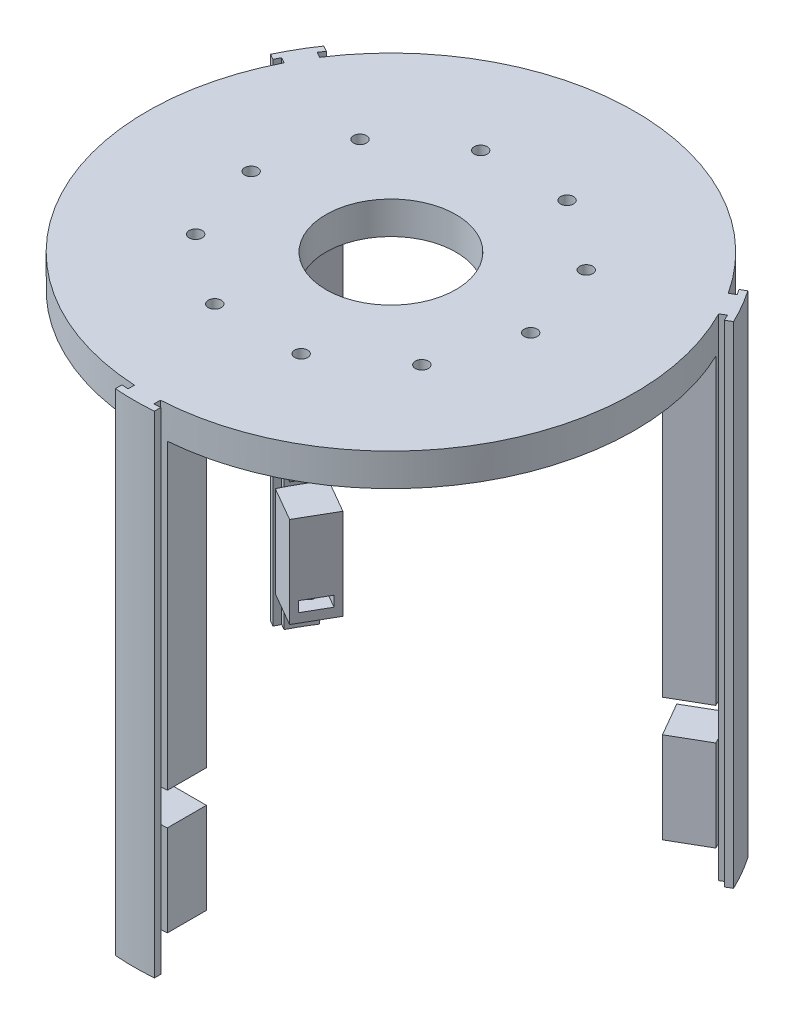
SolidWorks part; units mm, degrees
ref_plane "Front Plane" through (0, 0, 0) normal (0, 0, 1) x (1, 0, 0)
ref_plane "Top Plane" through (0, 0, 0) normal (0, 1, 0) x (1, 0, 0)
ref_plane "Right Plane" through (0, 0, 0) normal (1, 0, 0) x (0, 0, -1)
sketch "Sketch1" plane through (0, 0, 0) normal (0, 1, 0) x (1, 0, 0)
  circle A0 centre (0, 0) radius 37.5
  dimension "D1" = 75
extrude "Boss-Extrude1" add sketch "Sketch1" against normal blind 5
sketch "Sketch2" plane through (0, 0, 0) normal (0, 1, 0) x (1, 0, 0)
  line L0 (-2.75, 0) -> (2.75, 0) construction
  line L1 (0, 39.8902) -> (0, -39.5701) construction
  line L2 (0, -2.75) -> (0, 2.75) construction
  line L4 (-39.7283, 0) -> (39.0263, 0) construction
  circle A0 centre (-21.5, 0) radius 1
  circle A1 centre (-17.3939, 12.6374) radius 1
  circle A2 centre (-6.6439, 20.4477) radius 1
  circle A3 centre (6.6439, 20.4477) radius 1
  circle A4 centre (17.3939, 12.6374) radius 1
  circle A5 centre (21.5, 0) radius 1
  circle A6 centre (17.3939, -12.6374) radius 1
  circle A7 centre (6.6439, -20.4477) radius 1
  circle A8 centre (-6.6439, -20.4477) radius 1
  circle A9 centre (-17.3939, -12.6374) radius 1
  dimension "D1" = 10
  dimension "D2" = 43
extrude "Cut-Extrude1" cut sketch "Sketch2" against normal up to next
sketch "Sketch3" plane through (0, -5, 0) normal (0, -1, 0) x (1, 0, 0)
  line L0 (-3, 37.3798) -> (-3, 31.3798)
  line L1 (-3, 31.3798) -> (3, 31.3798)
  line L2 (3, 31.3798) -> (3, 37.3798)
  line L3 (33.8719, -16.0918) -> (28.6757, -13.0918)
  line L4 (28.6757, -13.0918) -> (25.6757, -18.288)
  line L5 (25.6757, -18.288) -> (30.8719, -21.288)
  line L6 (-30.8719, -21.288) -> (-25.6757, -18.288)
  line L7 (-25.6757, -18.288) -> (-28.6757, -13.0918)
  line L8 (-28.6757, -13.0918) -> (-33.8719, -16.0918)
  line L9 (0, 40.3758) -> (0, -39.6162) construction
  line L10 (0, -2.75) -> (0, 2.75) construction
  arc A0 (3, 37.3798) -> (-3, 37.3798) centre (0, 0) ccw
  arc A1 (30.8719, -21.288) -> (33.8719, -16.0918) centre (0, 0) ccw
  arc A2 (-33.8719, -16.0918) -> (-30.8719, -21.288) centre (0, 0) ccw
  circle A3 centre (0, 0) radius 37.5 construction
  point P18 (0, 0)
  dimension "D1" = 3
  dimension "D2" = 6
  dimension "D3" = 6
extrude "Boss-Extrude2" add sketch "Sketch3" along normal blind 65.5
sketch "Sketch4" plane through (0, -5, 0) normal (0, -1, 0) x (1, 0, 0)
  line L0 (-15.5255, 11.28) -> (-15.2841, 13.5767)
  line L1 (-19.1906, 0) -> (-20.3453, 2)
  line L2 (-20.3453, 2) -> (-22.6547, 2)
  line L3 (-22.6547, 2) -> (-23.8094, 0)
  line L4 (-23.8094, 0) -> (-22.6547, -2)
  line L5 (-22.6547, -2) -> (-20.3453, -2)
  line L6 (-20.3453, -2) -> (-19.1906, 0)
  line L7 (-15.2841, 13.5767) -> (-17.1525, 14.9341)
  line L8 (-17.1525, 14.9341) -> (-19.2622, 13.9948)
  line L9 (-19.2622, 13.9948) -> (-19.5036, 11.6981)
  line L10 (-19.5036, 11.6981) -> (-17.6353, 10.3406)
  line L11 (-17.6353, 10.3406) -> (-15.5255, 11.28)
  line L12 (-5.9302, 18.2513) -> (-4.3849, 19.9676)
  line L13 (-4.3849, 19.9676) -> (-5.0986, 22.1639)
  line L14 (-5.0986, 22.1639) -> (-7.3575, 22.6441)
  line L15 (-7.3575, 22.6441) -> (-8.9028, 20.9279)
  line L16 (-8.9028, 20.9279) -> (-8.1892, 18.7315)
  line L17 (-8.1892, 18.7315) -> (-5.9302, 18.2513)
  line L18 (5.9302, 18.2513) -> (8.1892, 18.7315)
  line L19 (8.1892, 18.7315) -> (8.9028, 20.9279)
  line L20 (8.9028, 20.9279) -> (7.3575, 22.6441)
  line L21 (7.3575, 22.6441) -> (5.0986, 22.1639)
  line L22 (5.0986, 22.1639) -> (4.3849, 19.9676)
  line L23 (4.3849, 19.9676) -> (5.9302, 18.2513)
  line L24 (15.5255, 11.28) -> (17.6353, 10.3406)
  line L25 (17.6353, 10.3406) -> (19.5036, 11.6981)
  line L26 (19.5036, 11.6981) -> (19.2622, 13.9948)
  line L27 (19.2622, 13.9948) -> (17.1525, 14.9341)
  line L28 (17.1525, 14.9341) -> (15.2841, 13.5767)
  line L29 (15.2841, 13.5767) -> (15.5255, 11.28)
  line L30 (19.1906, 0) -> (20.3453, -2)
  line L31 (20.3453, -2) -> (22.6547, -2)
  line L32 (22.6547, -2) -> (23.8094, 0)
  line L33 (23.8094, 0) -> (22.6547, 2)
  line L34 (22.6547, 2) -> (20.3453, 2)
  line L35 (20.3453, 2) -> (19.1906, 0)
  line L36 (15.5255, -11.28) -> (15.2841, -13.5767)
  line L37 (15.2841, -13.5767) -> (17.1525, -14.9341)
  line L38 (17.1525, -14.9341) -> (19.2622, -13.9948)
  line L39 (19.2622, -13.9948) -> (19.5036, -11.6981)
  line L40 (19.5036, -11.6981) -> (17.6353, -10.3406)
  line L41 (17.6353, -10.3406) -> (15.5255, -11.28)
  line L42 (5.9302, -18.2513) -> (4.3849, -19.9676)
  line L43 (4.3849, -19.9676) -> (5.0986, -22.1639)
  line L44 (5.0986, -22.1639) -> (7.3575, -22.6441)
  line L45 (7.3575, -22.6441) -> (8.9028, -20.9279)
  line L46 (8.9028, -20.9279) -> (8.1892, -18.7315)
  line L47 (8.1892, -18.7315) -> (5.9302, -18.2513)
  line L48 (-5.9302, -18.2513) -> (-8.1892, -18.7315)
  line L49 (-8.1892, -18.7315) -> (-8.9028, -20.9279)
  line L50 (-8.9028, -20.9279) -> (-7.3575, -22.6441)
  line L51 (-7.3575, -22.6441) -> (-5.0986, -22.1639)
  line L52 (-5.0986, -22.1639) -> (-4.3849, -19.9676)
  line L53 (-4.3849, -19.9676) -> (-5.9302, -18.2513)
  line L54 (-15.5255, -11.28) -> (-17.6353, -10.3406)
  line L55 (-17.6353, -10.3406) -> (-19.5036, -11.6981)
  line L56 (-19.5036, -11.6981) -> (-19.2622, -13.9948)
  line L57 (-19.2622, -13.9948) -> (-17.1525, -14.9341)
  line L58 (-17.1525, -14.9341) -> (-15.2841, -13.5767)
  line L59 (-15.2841, -13.5767) -> (-15.5255, -11.28)
  circle A0 centre (-21.5, 0) radius 2 construction
  dimension "D1" = 10
extrude "Cut-Extrude2" cut sketch "Sketch4" against normal blind 1.6
sketch "Sketch5" plane through (0, 0, 0) normal (0, 1, 0) x (1, 0, 0)
  line L0 (-3, -38.3602) -> (-3, -39.3859)
  line L1 (3, -38.381) -> (3, -39.3859)
  line L2 (2, -38.4461) -> (2, -37.4466)
  line L3 (-2, -38.4253) -> (-2, -37.4466)
  line L4 (-31.7209, 21.7782) -> (-32.6092, 22.291)
  line L5 (-34.739, 16.5924) -> (-35.6092, 17.0949)
  line L6 (-34.2953, 17.491) -> (-33.4297, 16.9913)
  line L7 (-32.2773, 20.9447) -> (-31.4297, 20.4554)
  line L8 (34.7209, 16.582) -> (35.6092, 17.0949)
  line L9 (31.739, 21.7886) -> (32.6092, 22.291)
  line L10 (32.2953, 20.9551) -> (31.4297, 20.4554)
  line L11 (34.2773, 17.4806) -> (33.4297, 16.9913)
  line L12 (0, 40.7328) -> (0, -41.0085) construction
  line L13 (0, -38.775) -> (0, 38.775) construction
  arc A0 (-3, -39.3859) -> (3, -39.3859) centre (0, 0) ccw
  arc A1 (-2, -37.4466) -> (2, -37.4466) centre (0, 0) ccw
  arc A2 (3, -38.381) -> (2, -38.4461) centre (0, 0) cw
  arc A3 (-3, -38.3602) -> (-2, -38.4253) centre (0, 0) ccw
  arc A4 (-32.6092, 22.291) -> (-35.6092, 17.0949) centre (0, 0) ccw
  arc A5 (-31.4297, 20.4554) -> (-33.4297, 16.9913) centre (0, 0) ccw
  arc A6 (-34.739, 16.5924) -> (-34.2953, 17.491) centre (0, 0) cw
  arc A7 (-31.7209, 21.7782) -> (-32.2773, 20.9447) centre (0, 0) ccw
  arc A8 (35.6092, 17.0949) -> (32.6092, 22.291) centre (0, 0) ccw
  arc A9 (33.4297, 16.9913) -> (31.4297, 20.4554) centre (0, 0) ccw
  arc A10 (31.739, 21.7886) -> (32.2953, 20.9551) centre (0, 0) cw
  arc A11 (34.7209, 16.582) -> (34.2773, 17.4806) centre (0, 0) ccw
  circle A12 centre (0, 0) radius 37.5 construction
  dimension "D1" = 3
  dimension "D2" = 6
  dimension "D3" = 2
  dimension "D4" = 1.0049
  dimension "D5" = 1
extrude "Boss-Extrude3" add sketch "Sketch5" against normal blind 75.5
sketch "Sketch6" plane through (0, 0, 0) normal (0, 1, 0) x (1, 0, 0)
  circle A0 centre (0, 0) radius 10
extrude "Cut-Extrude3" cut sketch "Sketch6" against normal up to next
sketch "Sketch7" plane through (0, 0, 0) normal (1, 0, 0) x (0, 0, -1)
  line L0 (0, 38.775) -> (0, -38.775) construction
  line L1 (0, -51.5) -> (-37.5, -51.5)
  line L2 (0, -51.5) -> (0, -56.5)
  line L3 (0, -56.5) -> (-37.5, -56.5)
  line L4 (-37.5, -51.5) -> (-37.5, -56.5)
  line L6 (-31.3798, -70.5) -> (-37.3798, -70.5) construction
  line L7 (0, -27.0167) -> (0, -72.0117) construction
  dimension "D1" = 37.5
  dimension "D2" = 5
  dimension "D3" = 14
revolve "Cut-Revolve1" cut sketch "Sketch7" angle 360 about L7
ref_plane "Plane5" through (0, -67.5, 0) normal (0, -1, 0) x (-1, 0, 0)
sketch "Sketch8" plane through (0, -67.5, 0) normal (0, -1, 0) x (-1, 0, 0)
  line L0 (0, 41.525) -> (0, -41.525) construction
  line L2 (-2, -31.3798) -> (-2, -35.5345)
  line L3 (-2, -35.5345) -> (0, -36.6892)
  line L4 (0, -36.6892) -> (2, -35.5345)
  line L5 (2, -35.5345) -> (2, -31.3798)
  line L7 (-3.1537, -34.3798) -> (3.1946, -34.3798) construction
  line L13 (0, -31.0997) -> (0, -37.7453) construction
  line L14 (3, -37.3798) -> (3, -31.3798) construction
  line L15 (-3, -31.3798) -> (-3, -37.3798) construction
  line L16 (-0.0081, -32.0751) -> (-2.0081, -33.2298) [skipped]
  line L17 (1.9919, -33.2204) -> (-0.0081, -32.0657) [skipped]
  line L18 (3, -31.3798) -> (-3, -31.3798) construction
  line L19 (3, -31.3798) -> (-3, -31.3798) construction
  line L20 (-2, -31.3798) -> (2, -31.3798)
  line L21 (-26.1757, 17.422) -> (-29.7738, 19.4993)
  line L22 (-29.7738, 19.4993) -> (-31.7738, 18.3446)
  line L23 (-31.7738, 18.3446) -> (-31.7738, 16.0352)
  line L24 (-31.7738, 16.0352) -> (-28.1757, 13.9579)
  line L25 (-26.1757, 17.422) -> (-28.1757, 13.9579)
  line L26 (-28.1969, 19.9211) -> (-31.3711, 14.4233) construction
  line L27 (-26.9332, 15.5499) -> (-32.6884, 18.8727) construction
  line L28 (28.1757, 13.9579) -> (31.7738, 16.0352)
  line L29 (31.7738, 16.0352) -> (31.7738, 18.3446)
  line L30 (31.7738, 18.3446) -> (29.7738, 19.4993)
  line L31 (29.7738, 19.4993) -> (26.1757, 17.422)
  line L32 (28.1757, 13.9579) -> (26.1757, 17.422)
  line L33 (31.3506, 14.4587) -> (28.1765, 19.9565) construction
  line L34 (26.9332, 15.5499) -> (32.6884, 18.8727) construction
  circle A0 centre (0, -34.3798) radius 2 construction
  circle A1 centre (-29.7738, 17.1899) radius 2 construction
  circle A2 centre (29.7738, 17.1899) radius 2 construction
  dimension "D1" = 3
extrude "Cut-Extrude4" cut sketch "Sketch8" along normal blind 1.6
sketch "Sketch9" plane through (0, -67.5, 0) normal (0, -1, 0) x (-1, 0, 0)
  line L0 (0, -31.1751) -> (0, -37.6667) construction
  line L1 (0, 41.525) -> (0, -41.525) construction
  line L2 (-3.1738, -34.4209) -> (3.1592, -34.4209) construction
  circle A0 centre (0, -34.4209) radius 1
  circle A1 centre (-29.8093, 17.2104) radius 1
  circle A2 centre (29.8093, 17.2104) radius 1
  dimension "D1" = 3
extrude "Cut-Extrude5" cut sketch "Sketch9" along normal up to surface (3 mm away) up to face at (0, -70.5, 35.4121)
